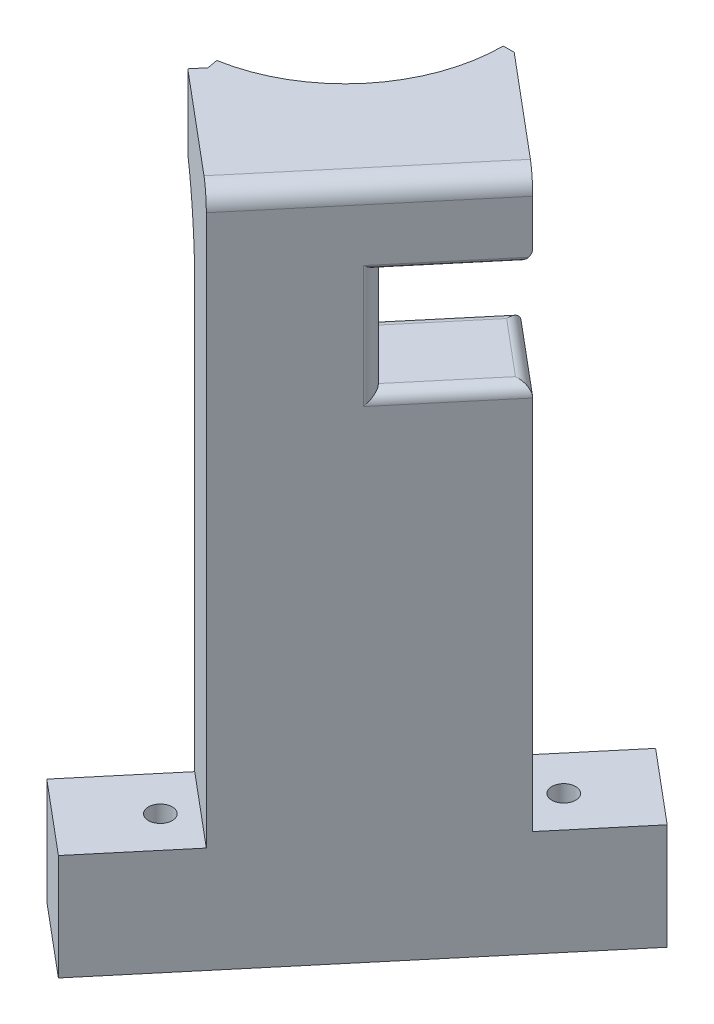
SolidWorks part; units mm, degrees
other "Markup1"
sketch "Sketch16" plane through (-5.2094, 14, 0) normal (0.4128, 0.8393, 0.3538) x (0.5563, 0.0753, -0.8276)
ref_plane "Front Plane" through (0, 0, 0) normal (0, 0, 1) x (1, 0, 0)
ref_plane "Top Plane" through (0, 0, 0) normal (0, 1, 0) x (1, 0, 0)
ref_plane "Right Plane" through (0, 0, 0) normal (1, 0, 0) x (0, 0, -1)
sketch "Sketch1" plane through (0, 0, 0) normal (0, 1, 0) x (1, 0, 0)
  line L0 (0, 0) -> (-45, 0)
  line L1 (0, 0) -> (-7.8142, 44.3163)
  circle A0 centre (0, 0) radius 42.1
  circle A1 centre (0, 0) radius 45
  circle A2 centre (0, 0) radius 30
  dimension "D1" = 84.2
  dimension "D2" = 90
  dimension "D3" = 60
  dimension "D4" = 80
extrude "Boss-Extrude1" add sketch "Sketch1" along normal blind 4 contours A2 L1 A0 L0 | L1 A1 L0 A0 region at (-25.6654, 0, -21.5358) region at (-43.55, 0, -0.5818)
extrude "Boss-Extrude2" add sketch "Sketch1<3>" along normal blind 14 contours L1 A1 L0 A0 region at (-43.55, 0, -0.5818)
sketch "Sketch1<3>" plane through (0, 0, 0) normal (0, 1, 0) x (1, 0, 0) same geometry as "Sketch1"
ref_plane "Plane1" through (0, -2.54, 0) normal (0, -1, 0) x (-1, 0, 0)
ref_plane "Plane2" through (0, -106.04, 0) normal (0, -1, 0) x (-1, 0, 0)
sketch "Sketch2" plane through (0, -106.04, 0) normal (0, -1, 0) x (-1, 0, 0)
  line L2 (7.8142, 44.3163) -> (5.2094, 29.5442)
  line L3 (30, 0) -> (45, 0)
  line L4 (7.8142, 44.3163) -> (5.2094, 29.5442)
  line L5 (30, 0) -> (45, 0)
  arc A2 (45, 0) -> (7.8142, 44.3163) centre (0, 0) ccw
  arc A3 (30, 0) -> (5.2094, 29.5442) centre (0, 0) ccw
  arc A4 (45, 0) -> (7.8142, 44.3163) centre (0, 0) ccw
  arc A5 (30, 0) -> (5.2094, 29.5442) centre (0, 0) ccw
  dimension "D1" = 0
sketch "Sketch3" plane through (0, 0, 0) normal (0, -1, 0) x (1, 0, 0)
  line L0 (-7.8142, -44.3163) -> (-45, 0)
  line L1 (-45, 0) -> (-75.6418, -25.7115)
  line L2 (-75.6418, -25.7115) -> (-38.4559, -70.0279)
  line L3 (-38.4559, -70.0279) -> (-7.8142, -44.3163)
  dimension "D1" = 40
extrude "Boss-Extrude3" add sketch "Sketch3" against normal up to surface (4 mm away) contours L3 L0 L1 L2 up to face at (-24.3855, 4, -20.4618)
sketch "Sketch4" plane through (0, 0, 0) normal (0, -1, 0) x (1, 0, 0)
  line L0 (-38.4559, -70.0279) -> (-19.3048, -53.9582)
  line L1 (-38.4559, -70.0279) -> (-7.8142, -44.3163) construction
  line L2 (-19.3048, -53.9582) -> (-56.4907, -9.6418)
  line L3 (-45, 0) -> (-75.6418, -25.7115) construction
  line L4 (-56.4907, -9.6418) -> (-75.6418, -25.7115)
  line L5 (-75.6418, -25.7115) -> (-38.4559, -70.0279)
  dimension "D1" = 25
extrude "Boss-Extrude4" add sketch "Sketch4" along normal blind 103.5
fillet "Fillet1" radius 20 1 edges at (-37.8978, 0, -31.8)
sketch "Sketch14" plane through (0, 4, 0) normal (0, 1, 0) x (1, 0, 0)
  line L0 (-7.8142, 44.3163) -> (-38.4559, 70.0279) construction
  line L1 (-38.4559, 70.0279) -> (-75.6418, 25.7115) construction
  line L2 (-75.6418, 25.7115) -> (-45, 0) construction
  line L9 (-7.3106, 41.4604) -> (-7.8142, 44.3163) construction
  line L10 (-45, 0) -> (-42.1, 0) construction
  line L12 (-7.8142, 44.3163) -> (-38.4559, 70.0279)
  line L13 (-38.4559, 70.0279) -> (-75.6418, 25.7115)
  line L14 (-75.6418, 25.7115) -> (-45, 0)
  line L15 (-7.3106, 41.4604) -> (-7.8142, 44.3163)
  line L16 (-45, 0) -> (-42.1, 0)
  arc A0 (-7.8142, 44.3163) -> (-45, 0) centre (0, 0) ccw construction
  arc A4 (-7.8142, 44.3163) -> (-45, 0) centre (0, 0) ccw construction
  arc A5 (-7.3106, 41.4604) -> (-42.1, 0) centre (0, 0) ccw construction
  arc A6 (-7.8142, 44.3163) -> (-45, 0) centre (0, 0) ccw
  arc A7 (-7.8142, 44.3163) -> (-45, 0) centre (0, 0) ccw
  arc A8 (-7.3106, 41.4604) -> (-42.1, 0) centre (0, 0) ccw
  arc M5 (-45, 0) -> (-7.8142, 44.3163) centre (0, 0) cw
  line M6 (-7.8142, 44.3163) -> (-38.4559, 70.0279)
  line M7 (-38.4559, 70.0279) -> (-75.6418, 25.7115)
  line M8 (-75.6418, 25.7115) -> (-45, 0)
extrude "Boss-Extrude7" add sketch "Sketch14" along normal blind 15 contours M8 M5 M6 M7 | A8 L15 L16 M5 region at (-44.3759, 4, -37.2358) region at (-8.1353, 4, -42.7874)
fillet "Fillet2" radius 5 1 edges at (-57.0489, 19, -47.8697)
sketch "Sketch6" plane through (18.5929, 0, -22.1582) normal (0.6428, 0, -0.766) x (-0.766, 0, -0.6428)
  line L0 (74.472, 14) -> (74.472, -103.5) construction
  line L1 (49.472, -103.5) -> (74.472, -103.5)
  line L2 (49.472, -103.5) -> (49.472, -97.5)
  line L3 (49.472, -97.5) -> (74.472, -97.5)
  line L4 (74.472, -103.5) -> (74.472, -97.5)
  dimension "D1" = 6
extrude "Boss-Extrude5" add sketch "Sketch6" along normal blind 25.4
sketch "Sketch7" plane through (-18.5929, 0, 22.1582) normal (-0.6428, 0, 0.766) x (0.766, 0, 0.6428)
  line L4 (-49.472, -103.5) -> (-49.472, -97.5)
  line L5 (-74.472, -103.5) -> (-49.472, -103.5)
  line L6 (-74.472, -97.5) -> (-74.472, -103.5)
  line L7 (-49.472, -97.5) -> (-74.472, -97.5)
  line L8 (-49.472, -103.5) -> (-49.472, -97.5)
  line L9 (-74.472, -103.5) -> (-49.472, -103.5)
  line L10 (-74.472, -97.5) -> (-74.472, -103.5)
  line L11 (-49.472, -97.5) -> (-74.472, -97.5)
  dimension "D1" = 0
extrude "Boss-Extrude6" add sketch "Sketch7" along normal blind 31.75
sketch "Sketch8" plane through (0, -97.5, 0) normal (0, 1, 0) x (1, 0, 0)
  circle A1 centre (-24.9091, 67.6646) radius 2.5527
  circle A2 centre (-24.9091, 67.6646) radius 2.5527
  circle A3 centre (-73.8895, 9.292) radius 2.5527
  circle A4 centre (-73.8895, 9.292) radius 2.5527
  dimension "D1" = 0
  dimension "D2" = 0
extrude "Cut-Extrude1" cut sketch "Sketch8" against normal blind 25.4 contours A4 | A2 region at (-73.8895, -97.5, -9.292)
sketch "Sketch9" plane through (0, -103.5, 0) normal (0, -1, 0) x (1, 0, 0)
  circle A0 centre (-73.8895, -9.292) radius 3.175
  circle A1 centre (-24.9091, -67.6646) radius 3.175
  dimension "D1" = 6.35
  dimension "D2" = 6.35
extrude "Cut-Extrude2" cut sketch "Sketch9" against normal blind 25.4
sketch "Sketch10" plane through (0, -97.5, 0) normal (0, 1, 0) x (1, 0, 0)
  line L1 (-76.8992, -14.6801) -> (-22.1291, -14.6801)
  line L2 (-76.8992, -14.6801) -> (-76.8992, 89.4854)
  line L3 (-76.8992, 89.4854) -> (-22.1291, 89.4854)
  line L4 (-22.1291, -14.6801) -> (-22.1291, 89.4854)
  line L5 (-144.4229, -81.7018) -> (69.164, -81.7018)
  line L6 (-144.4229, -81.7018) -> (-144.4229, 136.0266)
  line L7 (-144.4229, 136.0266) -> (69.164, 136.0266)
  line L8 (69.164, -81.7018) -> (69.164, 136.0266)
  line M11 (-75.6418, 25.7115) -> (-96.0503, 1.3896)
  line M12 (-96.0503, 1.3896) -> (-76.8992, -14.6801)
extrude "Cut-Extrude3" [suppressed] cut sketch "Sketch10" along normal blind 132.4 contours L5 L8 L7 L6 L4 L1 L2 L3 M12 M11 | L2 L1 L4 L3
ref_plane "Plane3" through (-64.7093, 0, -54.2976) normal (-0.766, 0, -0.6428) x (-0.6428, 0, 0.766)
sketch "Sketch18" plane through (0, -103.5, 0) normal (0, -1, 0) x (1, 0, 0)
  line L4 (-96.0503, -1.3896) -> (-22.1291, -89.4854)
  line L5 (-22.1291, -89.4854) -> (-2.978, -73.4157)
  line L6 (-2.978, -73.4157) -> (-76.8992, 14.6801)
  line L7 (-76.8992, 14.6801) -> (-96.0503, -1.3896)
  line L8 (-96.0503, -1.3896) -> (-22.1291, -89.4854)
  line L9 (-22.1291, -89.4854) -> (-2.978, -73.4157)
  line L10 (-2.978, -73.4157) -> (-76.8992, 14.6801)
  line L11 (-76.8992, 14.6801) -> (-96.0503, -1.3896)
  circle A1 centre (-24.9091, -67.6646) radius 3.175
  circle A2 centre (-24.9091, -67.6646) radius 3.175
  circle A3 centre (-73.8895, -9.292) radius 3.175
  circle A4 centre (-73.8895, -9.292) radius 3.175
  dimension "D1" = 0
  dimension "D2" = 0
  dimension "D3" = 0
extrude "Boss-Extrude9" add sketch "Sketch18" along normal blind 57.15
sketch "Sketch19" plane through (0, -97.5, 0) normal (0, 1, 0) x (1, 0, 0)
  line L0 (-56.4907, 9.6418) -> (-75.6418, 25.7115) construction
  line L1 (-75.6418, 25.7115) -> (-96.0503, 1.3896) construction
  line L2 (-96.0503, 1.3896) -> (-76.8992, -14.6801) construction
  line L3 (-76.8992, -14.6801) -> (-56.4907, 9.6418) construction
  line L4 (-38.4559, 70.0279) -> (-19.3048, 53.9582) construction
  line L5 (-19.3048, 53.9582) -> (-2.978, 73.4157) construction
  line L6 (-2.978, 73.4157) -> (-22.1291, 89.4854) construction
  line L7 (-22.1291, 89.4854) -> (-38.4559, 70.0279) construction
  line L8 (-56.4907, 9.6418) -> (-75.6418, 25.7115)
  line L9 (-75.6418, 25.7115) -> (-96.0503, 1.3896)
  line L10 (-96.0503, 1.3896) -> (-76.8992, -14.6801)
  line L11 (-76.8992, -14.6801) -> (-56.4907, 9.6418)
  line L12 (-38.4559, 70.0279) -> (-19.3048, 53.9582)
  line L13 (-19.3048, 53.9582) -> (-2.978, 73.4157)
  line L14 (-2.978, 73.4157) -> (-22.1291, 89.4854)
  line L15 (-22.1291, 89.4854) -> (-38.4559, 70.0279)
  circle A0 centre (-73.8895, 9.292) radius 3.175 construction
  circle A1 centre (-24.9091, 67.6646) radius 3.175 construction
  circle A2 centre (-73.8895, 9.292) radius 3.175
  circle A3 centre (-24.9091, 67.6646) radius 3.175
extrude "Cut-Extrude6" cut sketch "Sketch19" against normal blind 34.925
mirror "Mirror2" about plane through (-64.7093, 0, -54.2976) normal (-0.766, 0, -0.6428) of bodies 115 108
sketch "Sketch11" plane through (0, 19, 0) normal (0, 1, 0) x (1, 0, 0)
  line L0 (-67.6166, -74.3731) -> (52.0413, 76.7386)
  line L1 (52.0413, 76.7386) -> (-7.7876, 112.2458)
  line L2 (-7.7876, 112.2458) -> (-112.5342, -8.8462)
  line L3 (-112.5342, -8.8462) -> (-67.6166, -74.3731)
extrude "Cut-Extrude4" cut sketch "Sketch11" against normal through all both and the other way through all
sketch "Sketch13" plane through (-72.3698, 0, -60.7254) normal (0.766, 0, 0.6428) x (0.6428, 0, -0.766)
  line L0 (28.9254, 14) -> (28.9254, -132.425) construction
  line L1 (28.9254, -1) -> (0, -1)
  line L2 (28.9254, -1) -> (28.9254, -29.5)
  line L3 (28.9254, -29.5) -> (0, -29.5)
  line L4 (0, -1) -> (0, -29.5)
  line L6 (-28.9254, -103.5) -> (28.9254, -103.5)
  line L7 (-28.9254, 14) -> (-28.9254, -132.425) construction
  line L8 (28.9254, 14) -> (28.9254, -132.425) construction
  line L10 (-60.6754, -160.65) -> (54.3254, -160.65) construction
  line M11 (28.9254, -132.425) -> (28.9254, 14)
  dimension "D1" = 57.15
  dimension "D2" = 28.5
  dimension "D3" = 74
extrude "Cut-Extrude5" cut sketch "Sketch13" against normal blind 85 contours L1 L4 L3 M11 region at (-63.0733, -15.25, -71.8045)
fillet "Fillet3" radius 3 7 edges at (-94.0045, -9.0764, -78.8791) (-91.5209, -24.7465, -76.7951) (-82.2244, -29.5, -87.8742) (-63.3524, -29.5, -90.9185) (-63.0733, -29.5, -71.8045) (-72.3698, -15.25, -60.7254) (-68.6209, -1, -95.3392)
fillet "Fillet4" radius 1 1 edges at (-65.0017, -1, -69.5064) tangent propagation no
sketch "Sketch15" plane through (-18.5929, 0, 22.1582) normal (-0.6428, 0, 0.766) x (0.766, 0, 0.6428)
  line L5 (-119.472, -132.425) -> (-94.472, -132.425)
  line L6 (-94.472, -132.425) -> (-94.472, 14)
  line L7 (-99.472, 19) -> (-134.472, 19)
  line L8 (-134.472, 19) -> (-134.472, -0.6351)
  line L9 (-119.472, -20) -> (-119.472, -132.425)
  line L11 (-94.472, -132.425) -> (-94.472, 14)
  line L13 (-134.472, 19) -> (-134.472, -0.6351)
  line L14 (-119.472, -20) -> (-119.472, -132.425)
  line L16 (-99.472, 19) -> (-134.472, 19)
  line L18 (-119.472, -132.425) -> (-94.472, -132.425)
  arc A2 (-94.472, 14) -> (-99.472, 19) centre (-99.472, 14) ccw
  arc A3 (-119.472, -20) -> (-134.472, -0.6351) centre (-139.472, -20) ccw
  arc A5 (-119.472, -20) -> (-134.472, -0.6351) centre (-139.472, -20) ccw
  arc A6 (-94.472, 14) -> (-99.472, 19) centre (-99.472, 14) ccw
  dimension "D1" = 0
extrude "Boss-Extrude8" add sketch "Sketch15" along normal blind 3.81
